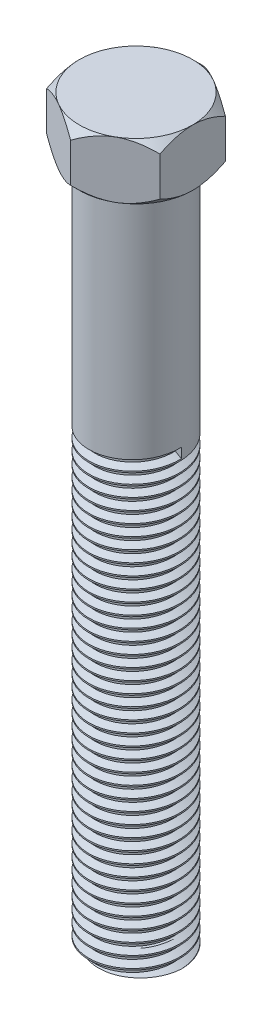
SolidWorks part; units mm, degrees
ref_plane "Alzado" through (0, 0, 0) normal (0, 0, 1) x (1, 0, 0)
ref_plane "Planta" through (0, 0, 0) normal (0, 1, 0) x (1, 0, 0)
ref_plane "Vista lateral" through (0, 0, 0) normal (1, 0, 0) x (0, 0, -1)
sketch "Croquis1" plane through (0, 0, 0) normal (0, 1, 0) x (1, 0, 0)
  line L1 (0, -5.7735) -> (5, -2.8868)
  line L2 (5, -2.8868) -> (5, 2.8868)
  line L3 (5, 2.8868) -> (0, 5.7735)
  line L4 (0, 5.7735) -> (-5, 2.8868)
  line L5 (-5, 2.8868) -> (-5, -2.8868)
  line L6 (-5, -2.8868) -> (0, -5.7735)
  circle A0 centre (0, 0) radius 5 construction
  dimension "D1" = 10
extrude "Saliente-Extruir1" add sketch "Croquis1" along normal mid plane 5
sketch "Croquis3" plane through (0, -2.5, 0) normal (0, -1, 0) x (1, 0, 0)
  circle A0 centre (0, 0) radius 4
  dimension "D1" = 8
extrude "Saliente-Extruir3" add sketch "Croquis3" along normal blind 60
sketch "Croquis4" plane through (0, -2.5, 0) normal (0, -1, 0) x (1, 0, 0)
  circle A0 centre (0, 0) radius 5
  dimension "D1" = 10
extrude "Cortar-Extruir1" cut sketch "Croquis4" against normal blind 30 draft 45 flip side to cut
mirror "Simetría1" about plane through (0, 0, 0) normal (0, 1, 0) of "Cortar-Extruir1"
thread "Rosca1" pitch 1 method cut profile "Perfil de rosca3" start angle 0, offset 1, length 40, pitch 1, diameter 8
ref_plane "Plano3" through (4, -63.5, 0) normal (0, 0, 1) x (1, 0, 0)
sketch "Perfil de rosca3" plane through (4, -63.5, 0) normal (0, 0, 1) x (1, 0, 0)
  line L0 (0, 0) -> (0, 1) construction
  line L11 (0, 0) -> (0, 0.875)
  line L12 (0, 0.875) -> (-0.5413, 0.5625)
  line L13 (-0.5413, 0.5625) -> (-0.5413, 0.3125)
  line L15 (-0.5413, 0.3125) -> (0, 0)
  line L17 (-0.5413, 0.4375) -> (0, 0.4375) construction
  point P2 (0, 0)
  dimension "Pitch" = 1
  dimension "Profile_Angle" = 60
  dimension "Profile_Land" = 0.25
  dimension "Profile_Height" = 0.5413
sketch "Croquis22" plane through (0, -62.5, 0) normal (0, -1, 0) x (1, 0, 0)
  circle A0 centre (0, 0) radius 4
